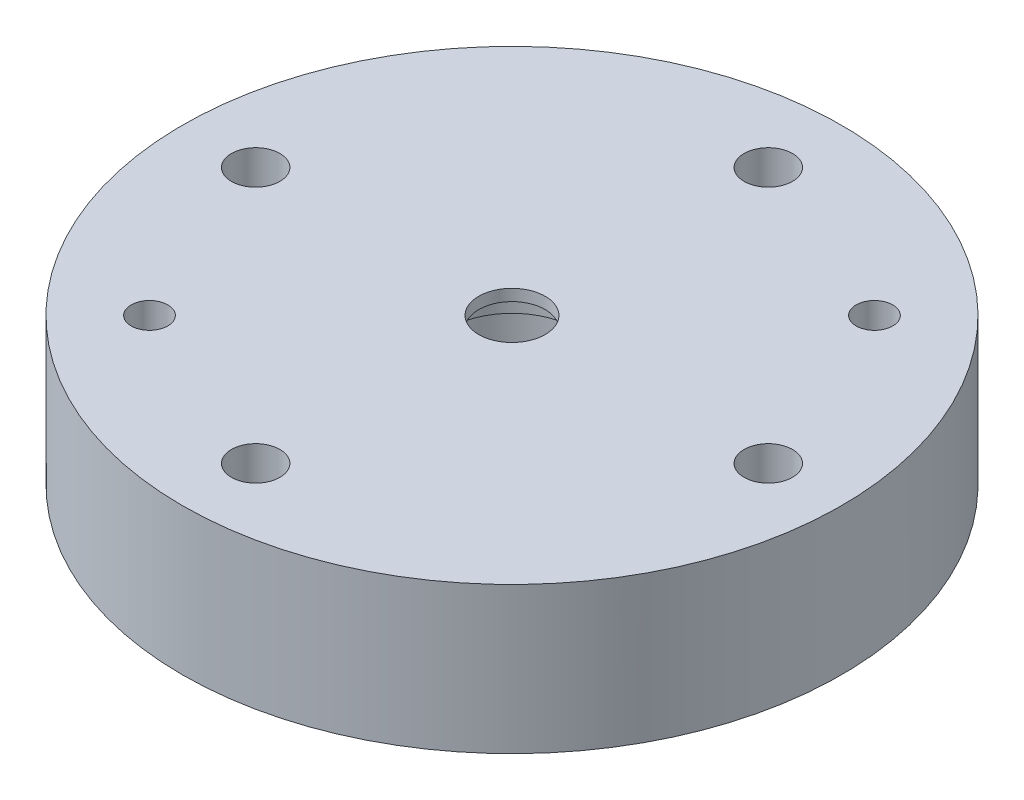
SolidWorks part; units mm, degrees
ref_plane "Front Plane" through (0, 0, 0) normal (0, 0, 1) x (1, 0, 0)
ref_plane "Top Plane" through (0, 0, 0) normal (0, 1, 0) x (1, 0, 0)
ref_plane "Right Plane" through (0, 0, 0) normal (1, 0, 0) x (0, 0, -1)
sketch "Sketch1" plane through (0, 0, 0) normal (0, 1, 0) x (1, 0, 0)
  circle A0 centre (0, 0) radius 57.15
  dimension "D1" = 114.3
extrude "seal seat hieght" add sketch "Sketch1" against normal blind 5.5372 contours A0
ref_plane "top end of seal" through (0, 0, 0) normal (0, 1, 0) x (1, 0, 0)
sketch "Sketch2" plane through (0, -5.5372, 0) normal (0, -1, 0) x (1, 0, 0)
  circle A1 centre (0, 0) radius 57.15
  circle A2 centre (0, 0) radius 57.15
  dimension "D1" = 0
extrude "seal diaphram hieght" add sketch "Sketch2" along normal blind 15.875
ref_plane "bottom end of seal" through (0, -21.4122, 0) normal (0, -1, 0) x (-1, 0, 0)
sketch "Sketch3" plane through (0, 0, 0) normal (0, 1, 0) x (1, 0, 0)
  circle A1 centre (0, 0) radius 57.15
  circle A2 centre (0, 0) radius 57.15
  dimension "D1" = 0
extrude "seal shoulder hieght" add sketch "Sketch3" along normal blind 2
sketch "Sketch4" plane through (0, -21.4122, 0) normal (0, -1, 0) x (1, 0, 0)
  circle A1 centre (0, 0) radius 57.15
  circle A2 centre (0, 0) radius 57.15
  dimension "D1" = 0
extrude "bottom seal clearance" add sketch "Sketch4" along normal blind 2
sketch "Sketch5" plane through (0, 0, 0) normal (0, 1, 0) x (1, 0, 0)
  circle A0 centre (0, 0) radius 11.1125
  dimension "D1" = 22.225
extrude "seal seat fit" cut sketch "Sketch5" against normal blind 5.5372
sketch "Sketch6" plane through (0, -21.4122, 0) normal (0, -1, 0) x (-1, 0, 0)
  circle A0 centre (0, 0) radius 12.7
  dimension "D1" = 25.4
extrude "seal diaphram clearance" cut sketch "Sketch6" against normal blind 15.875 and the other way up to surface (2 mm away) other way up to face at (0, -23.4122, -57.15)
sketch "Sketch7" plane through (0, 0, 0) normal (0, 1, 0) x (1, 0, 0)
  circle A0 centre (0, 0) radius 4.7625 construction
  circle A1 centre (0, 0) radius 5.7625
  dimension "D1" = 9.525
  dimension "D2" = 1
extrude "shaft clearance" cut sketch "Sketch7" along normal up to surface (2 mm away) up to face at (0, 2, 57.15)
sketch "bolt circle" plane through (0, 2, 0) normal (0, 1, 0) x (1, 0, 0)
  circle A0 centre (0, 0) radius 44.45 construction
  point P3 (-44.45, 0)
  point P4 (0, 44.45)
  point P5 (44.45, 0)
  point P6 (0, -44.45)
  dimension "D1" = 88.9
hole_wizard "M8 Clearance Hole1" positions "Sketch11" profile "Sketch12" hole size "M8" standard "ANSI Metric" end condition through all
sketch "Sketch11" plane through (0, 2, 0) normal (0, 1, 0) x (1, 0, 0)
  point P0 (-44.45, 0)
  point P3 (0, 44.45)
  point P6 (44.45, 0)
  point P9 (0, -44.45)
sketch "Sketch12" plane through (-44.45, 2, 0) normal (1, 0, 0) x (0, 0, 1)
  line L0 (0, 0) -> (0, 25.4122)
  line L1 (0, 25.4122) -> (4.2, 25.4122)
  line L2 (4.2, 25.4122) -> (4.2, 0)
  line L5 (4.2, 0) -> (0, 0)
  line L11 (0, -6.35) -> (0, 107.95) construction
  dimension "Thru Hole Dia." = 8.4
  dimension "Thru Hole Depth" = 25.4122
sketch "dowel hole positioning " plane through (0, 2, 0) normal (0, 1, 0) x (1, 0, 0)
  line L0 (0, 0) -> (53.8672, 0) construction
  line L1 (-31.4309, -31.4309) -> (31.4309, 31.4309) construction
  circle A0 centre (0, 0) radius 44.45 construction
  circle A1 centre (0, 0) radius 44.45 construction
  point P8 (0, 0)
  point P9 (31.4309, 31.4309)
  point P10 (-31.4309, -31.4309)
  dimension "D1" = 45
hole_wizard "1/4 (0.25) Press Dowel Hole1" positions "Sketch14" profile "Sketch15" hole size "1/4" standard "ANSI Inch" end condition through all
sketch "Sketch14" plane through (0, 2, 0) normal (0, 1, 0) x (1, 0, 0)
  point P0 (31.4309, 31.4309)
  point P3 (-31.4309, -31.4309)
sketch "Sketch15" plane through (31.4309, 2, -31.4309) normal (1, 0, 0) x (0, 0, 1)
  line L0 (0, 0) -> (0, 25.4122)
  line L1 (0, 25.4122) -> (3.175, 25.4122)
  line L2 (3.175, 25.4122) -> (3.175, 0)
  line L5 (3.175, 0) -> (0, 0)
  line L11 (0, -6.35) -> (0, 107.95) construction
  dimension "Thru Hole Dia." = 6.35
  dimension "Thru Hole Depth" = 25.4122
equation "\"seal seat height\"=5.5372"
equation "\"D1@seal seat hieght\" = \"seal seat height\""
equation "\"seal diaphram height\"=15.875"
equation "\"D1@seal diaphram hieght\" = \"seal diaphram height\""
equation "\"seal shoulder height\"=2"
equation "\"D1@seal shoulder hieght\" = \"seal shoulder height\""
equation "\"seal seat OD\"= .875in"
equation "\"D1@Sketch5\"=\"seal seat OD\""
equation "\"D1@seal seat fit\" = \"seal seat height\""
equation "\"seal diaphram clearance\"=25.4"
equation "\"D1@Sketch6\"=\"seal diaphram clearance\""
equation "\"D1@seal diaphram clearance\" = \"seal diaphram height\""
equation "\"seal ID\"=9.525"
equation "\"D1@Sketch7\"=\"seal ID\""
equation "\"bolt circle dia\"=88.9"
equation "\"D1@bolt circle\" = \"bolt circle dia\""
